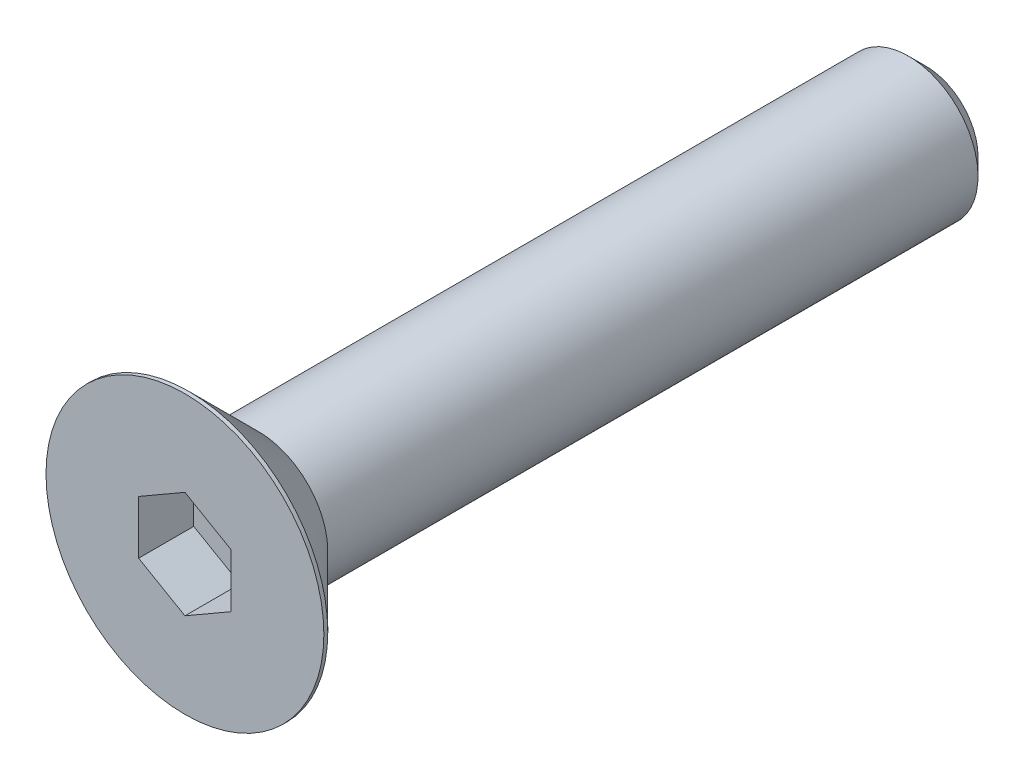
SolidWorks part; units mm, degrees
material "Chrome Stainless Steel"
ref_plane "Front" through (0, 0, 0) normal (0, 0, 1) x (1, 0, 0)
ref_plane "Top" through (0, 0, 0) normal (0, 1, 0) x (1, 0, 0)
ref_plane "Right" through (0, 0, 0) normal (1, 0, 0) x (0, 0, -1)
sketch "Sketch11" plane through (0, 0, 0) normal (1, 0, 0) x (0, 0, -1)
  line L0 (-8, 3) -> (8, 3) construction
  line L5 (-8, 3) -> (-8, -3) construction
  line L6 (8, 1.5) -> (8, -1.5) construction
  line L7 (-7.99, 1) -> (-7.99, -1) construction
  line L8 (7.9688, 1.5541) -> (8.4688, 1.5541) construction
  line L9 (8.4688, 1.5541) -> (8.2188, 1.1211) construction
  line L10 (8.2188, 1.1211) -> (7.9688, 1.5541) construction
  line L11 (8.1875, 1.1752) -> (8.25, 1.1752) construction
  line L12 (8.2188, 1.1752) -> (8.2188, 1.1211) construction
  line L13 (7.9844, 1.5271) -> (8.4531, 1.5271) construction
  line L14 (8.2188, 1.5541) -> (8.2188, 1.5) construction
  line L15 (8, 1.5) -> (8.4375, 1.5) construction
  line L17 (-7.915, 3) -> (-4.915, 0) construction
  line L18 (-4.915, 0) -> (-7.915, -3) construction
  point P3 (-6.3, 3)
  point P8 (0, 3)
  point P21 (8.2188, 1.5271)
  point P26 (-8, 0)
  point P28 (-7.99, 0)
  point P29 (8, 0)
  dimension "Length" = 16
  dimension "Head Diameter" = 6
  dimension "Thread Major Diameter" = 3
  dimension "Head Height" = 1.7
  dimension "Drive Size" = 2
  dimension "Thread Pitch" = 0.5
  dimension "D1" = 0.0625
  dimension "D2" = 0.01
  dimension "D3" = 0.085
  dimension "Countersink Angle" = 90
sketch "Sketch1" plane through (0, 0, 0) normal (1, 0, 0) x (0, 0, -1)
  line L2 (-6.3, 1.5) -> (8, 1.5)
  line L3 (8, 1.5) -> (8, 0)
  line L4 (-6.81, 1.5) -> (-6.81, 0)
  line L5 (-6.3, 1.5) -> (-6.81, 1.5)
  line L6 (-8, 3) -> (-8, -3) construction
  line L7 (8, 1.5) -> (8, -1.5) construction
  line L8 (-6.81, 0) -> (8, 0)
  dimension "D1" = 1.19
revolve "Revolve1" add sketch "Sketch1" angle 360 mid plane about L8
chamfer "Chamfer1" distance 0.375 angle 45 1 edges at (0, -1.5, -8)
sketch "Sketch7" plane through (0, 0, 0) normal (1, 0, 0) x (0, 0, -1)
  line L2 (-8, 3) -> (-7.915, 3)
  line L5 (-6.3, 1.385) -> (-6.3, 0)
  line L6 (-8, 3) -> (-8, 0)
  line L8 (-8, 3) -> (-8, -3) construction
  line L9 (-8, 0) -> (-6.3, 0)
  line L12 (-7.915, 3) -> (-6.3, 1.385)
  line L13 (-7.915, 3) -> (-4.915, 0) construction
revolve "Revolve2" add sketch "Sketch7" angle 360 mid plane about L9 region at (0, 1.1696, 7.2571)
ref_plane "Plane1" through (0, 0, 6.3) normal (0, 0, 1) x (1, 0, 0)
sketch "Sketch5" plane through (0, 0, 8) normal (0, 0, 1) x (1, 0, 0)
  line L1 (1, -0.5774) -> (1, 0.5774)
  line L2 (1, 0.5774) -> (0, 1.1547)
  line L3 (0, 1.1547) -> (-1, 0.5774)
  line L4 (-1, 0.5774) -> (-1, -0.5774)
  line L5 (-1, -0.5774) -> (0, -1.1547)
  line L6 (0, -1.1547) -> (1, -0.5774)
  circle A0 centre (0, 0) radius 1 construction
extrude "Cut-Extrude2" cut sketch "Sketch5" against normal blind 1.19
sketch "Sketch6" plane through (0, 0, 8) normal (0, 0, -1) x (-1, 0, 0)
  circle A0 centre (0, 0) radius 1.1547
extrude "Cut-Extrude3" [suppressed] cut sketch "Sketch6" along normal blind 1.19 draft 45
sketch "Sketch12" [suppressed] plane through (0, 0, -8) normal (0, 0, -1) x (-1, 0, 0)
  circle A0 centre (0, 0) radius 1.5 construction
  circle A1 centre (0, 0) radius 1.5
curve "Helix/Spiral1" [suppressed] pitch 0.5 height 16 turns 32
sketch "Sketch13" [suppressed] plane through (0, 0, 0) normal (1, 0, 0) x (0, 0, -1)
  line L0 (7.9844, 1.5271) -> (8.4531, 1.5271)
  line L1 (8.4531, 1.5271) -> (8.25, 1.1752)
  line L2 (8.25, 1.1752) -> (8.1875, 1.1752)
  line L3 (8.1875, 1.1752) -> (7.9844, 1.5271)
sweep "Cut-Sweep1" [suppressed] cut profiles "Sketch13" path "Helix/Spiral1"
combine bodies "Combine1" [suppressed] operation type add bodies to combine 113 127
equation "\"D1@Chamfer1\"=\"Thread Pitch@Sketch11\" * .75"
equation "\"D1@Cut-Extrude2\"= \"Head Height@Sketch11\" * .7"
equation "\"D1@Cut-Extrude3\" = \"D1@Cut-Extrude2\""
equation "\"D1@Sketch11\"=\"Thread Pitch@Sketch11\"/8"
equation "\"D3@Sketch11\"=\"Head Height@Sketch11\"*.05"
equation "\"D4@Helix/Spiral1\"=\"Thread Pitch@Sketch11\""
equation "\"D1@Sketch1\"=\"Head Height@Sketch11\"*.7"
equation "\"D3@Helix/Spiral1\"=\"Length@Sketch11\""
